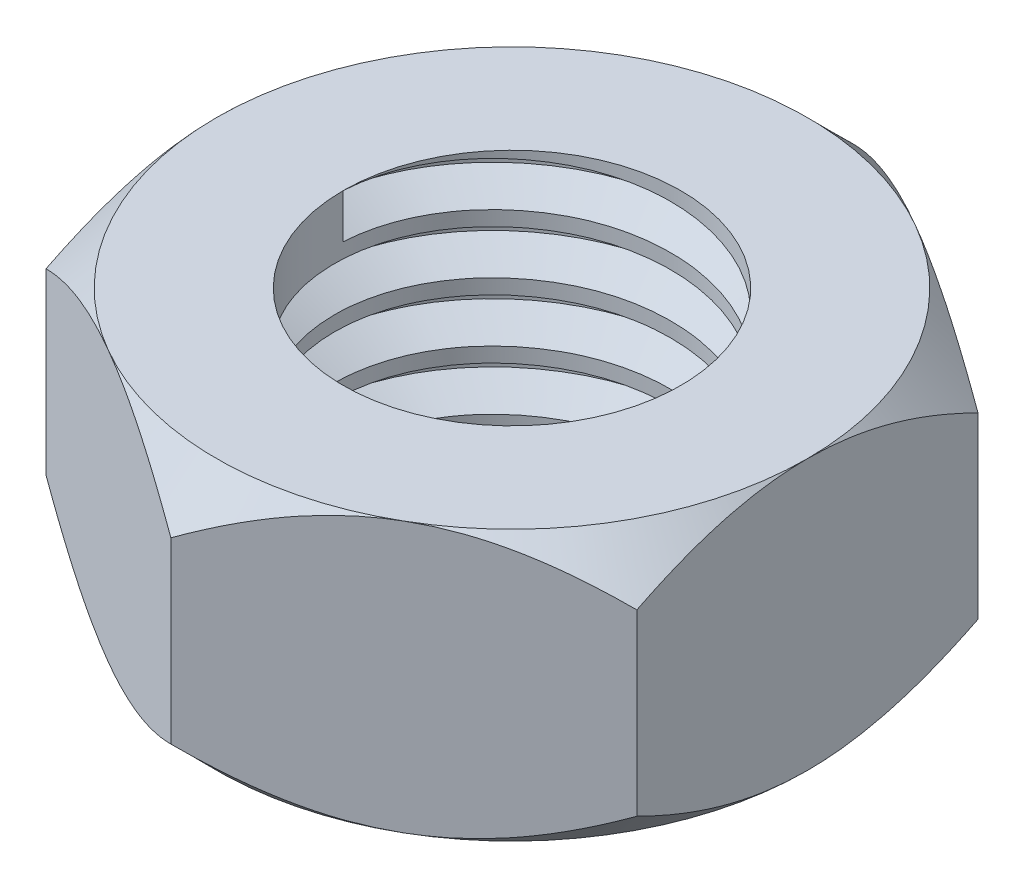
SolidWorks part; units mm, degrees
ref_plane "Front Plane" through (0, 0, 0) normal (0, 0, 1) x (1, 0, 0)
ref_plane "Top Plane" through (0, 0, 0) normal (0, 1, 0) x (1, 0, 0)
ref_plane "Right Plane" through (0, 0, 0) normal (1, 0, 0) x (0, 0, -1)
sketch "Sketch1" plane through (0, 0, 0) normal (0, 1, 0) x (1, 0, 0)
  line L1 (0, 4.0415) -> (-3.5, 2.0207)
  line L2 (-3.5, 2.0207) -> (-3.5, -2.0207)
  line L3 (-3.5, -2.0207) -> (0, -4.0415)
  line L4 (0, -4.0415) -> (3.5, -2.0207)
  line L5 (3.5, -2.0207) -> (3.5, 2.0207)
  line L6 (3.5, 2.0207) -> (0, 4.0415)
  circle A0 centre (0, 0) radius 3.5 construction
  dimension "D1" = 7
extrude "Boss-Extrude2" add sketch "Sketch1" along normal blind 3.2
sketch "Sketch2" plane through (0, 3.2, 0) normal (0, 1, 0) x (1, 0, 0)
  circle A0 centre (0, 0) radius 2
  dimension "D1" = 4
extrude "Cut-Extrude2" cut sketch "Sketch2" against normal through all
sketch "Sketch3" plane through (0, 3.2, 0) normal (0, 1, 0) x (1, 0, 0)
  line L0 (3.5, -2.0207) -> (3.5, 2.0207) construction
  circle A0 centre (0, 0) radius 3.5
extrude "Cut-Extrude3" cut sketch "Sketch3" against normal blind 3.2 draft 45 flip side to cut
sketch "Sketch4" plane through (0, 0, 0) normal (0, -1, 0) x (1, 0, 0)
  line L0 (-3.5, -2.0207) -> (-3.5, 2.0207) construction
  circle A0 centre (0, 0) radius 3.5
extrude "Cut-Extrude4" cut sketch "Sketch4" against normal blind 3.2 draft 45 flip side to cut
thread "Thread1" pitch 0.7 method cut profile "Thread Profile1" start angle 0, offset 0, length 4, pitch 0.7, diameter 4
ref_plane "Plane1" through (-2, 3.2, 0) normal (0, 0, 1) x (-1, 0, 0)
sketch "Thread Profile1" plane through (-2, 3.2, 0) normal (0, 0, 1) x (-1, 0, 0)
  line L0 (0, 0) -> (0, 0.7) construction
  line L1 (0, 0) -> (0.3789, 0.2187)
  line L2 (0.3789, 0.2187) -> (0.3789, 0.3062)
  line L3 (0.3789, 0.3062) -> (0, 0.525)
  line L4 (0.3789, 0.2625) -> (0, 0.2625) construction
  line L11 (0, 0) -> (0, 0.525)
  point P2 (0, 0)
  dimension "Pitch" = 0.7
  dimension "Profile_Angle" = 60
  dimension "Profile_Land" = 0.0875
  dimension "Profile_Height" = 0.3789
